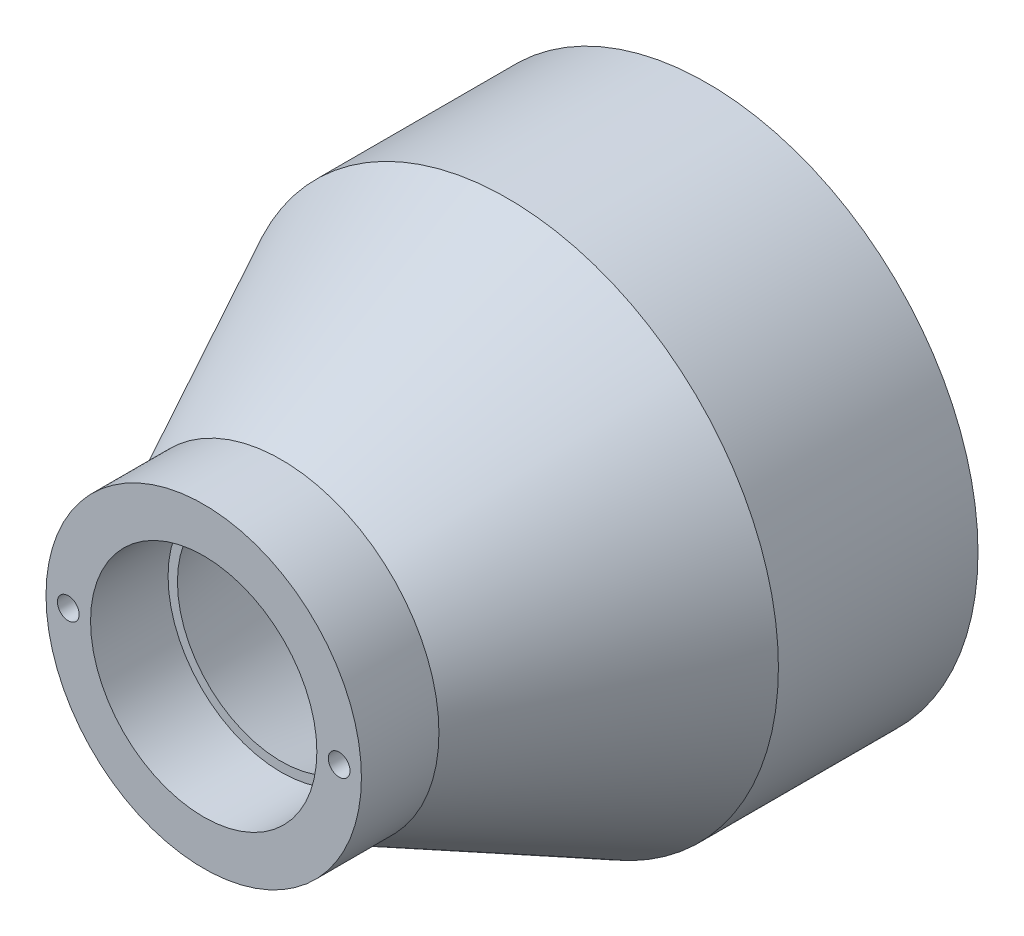
SolidWorks part; units mm, degrees
ref_plane "Plan de face" through (0, 0, 0) normal (0, 0, 1) x (1, 0, 0)
ref_plane "Plan de dessus" through (0, 0, 0) normal (0, 1, 0) x (1, 0, 0)
ref_plane "Plan de droite" through (0, 0, 0) normal (1, 0, 0) x (0, 0, -1)
sketch "Esquisse1" plane through (0, 0, 0) normal (0, 0, 1) x (1, 0, 0)
  circle A0 centre (0, 0) radius 12.7
  circle A1 centre (0, 0) radius 17.7
extrude "Boss.-Extru.1" add sketch "Esquisse1" along normal blind 8.7
sketch "Esquisse2" plane through (0, 0, 0) normal (0, 0, -1) x (-1, 0, 0)
  circle A0 centre (0, 0) radius 11.2
  circle A1 centre (0, 0) radius 30.4
extrude "Boss.-Extru.2" add sketch "Esquisse2" along normal blind 47.8
chamfer "Chanfrein1" distance 25.4 angle 26.565 1 edges at (-30.4, 0, 0) first distance on face at (-30.4, 0, -47.8)
chamfer "Chanfrein3" distance 49.8 angle 12.675 1 edges at (-11.2, 0, -47.8) first distance on face at (-11.2, 0, -47.8)
sketch "Sketch1" plane through (0, 0, 8.7) normal (0, 0, 1) x (1, 0, 0)
  line L0 (-12.7, 0) -> (-17.7, 0)
  line L1 (-17.7, 0) -> (12.7, 0)
  line L2 (12.7, 0) -> (17.7, 0)
  circle A0 centre (0, 0) radius 12.7 construction
  circle A1 centre (0, 0) radius 12.7 construction
  circle A2 centre (0, 0) radius 17.7 construction
hole_wizard "#41 (0.096) Diameter Hole1" positions "Sketch2" profile "Sketch4" hole size "#41" standard "ANSI Inch"
sketch "Sketch2" plane through (0, 0, 8.7) normal (0, 0, 1) x (1, 0, 0)
  line L0 (-12.7, 0) -> (-17.7, 0) construction
  line L1 (12.7, 0) -> (17.7, 0) construction
  point P0 (-15.2, 0)
  point P4 (15.2, 0)
sketch "Sketch4" plane through (-15.2, 0, 8.7) normal (1, 0, 0) x (0, -1, 0)
  line L0 (0, 0) -> (0, 5.7326)
  line L1 (0, 5.7326) -> (1.2192, 5)
  line L2 (1.2192, 5) -> (1.2192, 0)
  line L5 (1.2192, 0) -> (0, 0)
  line L10 (0, 5.7326) -> (-1.2192, 5) construction
  line L11 (0, -6.35) -> (0, 107.95) construction
  dimension "Hole Dia." = 2.4384
  dimension "Hole Depth" = 5
  dimension "Drill Angle" = 118
